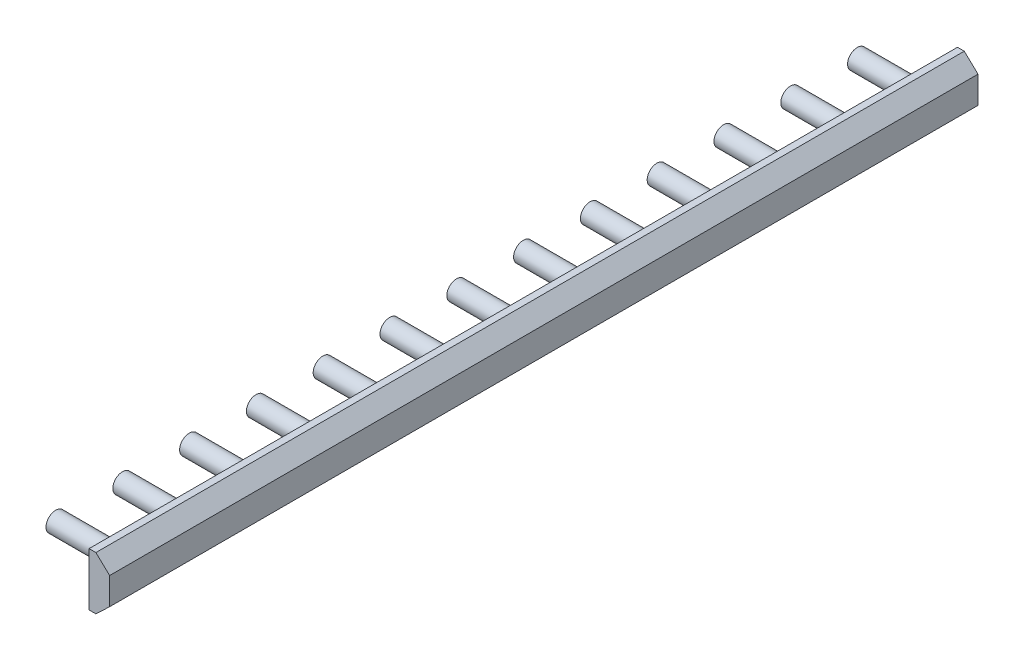
SolidWorks part; units mm, degrees
ref_plane "Front Plane" through (0, 0, 0) normal (0, 0, 1) x (1, 0, 0)
ref_plane "Top Plane" through (0, 0, 0) normal (0, 1, 0) x (1, 0, 0)
ref_plane "Right Plane" through (0, 0, 0) normal (1, 0, 0) x (0, 0, -1)
sketch "Sketch1" plane through (0, 0, 0) normal (0, 0, 1) x (1, 0, 0)
  line B0 (0, 7.95) -> (2.04, 7.95)
  line B1 (6.1524, 4.048) -> (6.1524, -4.048)
  line B2 (2.04, -7.95) -> (0, -7.95)
  line B3 (0, -7.95) -> (0, 7.95)
  line B4 (2.04, 7.95) -> (6.1524, 4.048)
  line B5 (6.1524, -4.048) -> (2.04, -7.95)
sketch_block_instance "Extrusion Profile-1"
sketch_block "Extrusion Profile" parameters "D1"=8.44, "D2"=2.6, "D3"=6, "D4"=16.7, "D6"=5.6686, "D7"=2.0404, "D8"=8.0963, "D9"=15.9, "D5"=2.4157
extrude "Boss-Extrude1" add sketch "Sketch1" along normal blind 260
sketch "Sketch2" plane through (0, 0, 0) normal (-1, 0, 0) x (0, 0, 1)
  circle A0 centre (10, 0) radius 2.9
  circle A1 centre (30, 0) radius 2.9
  circle A2 centre (50, 0) radius 2.9
  circle A3 centre (70, 0) radius 2.9
  circle A4 centre (90, 0) radius 2.9
  circle A5 centre (110, 0) radius 2.9
  circle A6 centre (130, 0) radius 2.9
  circle A7 centre (150, 0) radius 2.9
  circle A8 centre (170, 0) radius 2.9
  circle A9 centre (190, 0) radius 2.9
  circle A10 centre (210, 0) radius 2.9
  circle A11 centre (230, 0) radius 2.9
  circle A12 centre (250, 0) radius 2.9
  dimension "D2" = 5.8
  dimension "D1" = 10
  dimension "D4" = 20
  dimension "D3" = 13
extrude "Boss-Extrude2" add sketch "Sketch2" along normal blind 20
sketch "Sketch3" [suppressed] plane through (0, 0, 0) normal (-1, 0, 0) x (0, 0, 1)
  line L0 (190, 0) -> (210, 0) construction
  line L1 (200, 0) -> (200, 7.95) construction
  line L2 (260, 7.95) -> (0, 7.95) construction
  line L3 (200, 7.95) -> (200, 7)
  line L4 (200, 7) -> (100, 7)
  line L5 (100, 7) -> (100, 7.95)
  line L6 (100, 7.95) -> (200, 7.95)
  line L7 (90, 0) -> (110, 0) construction
  line L8 (100, 0) -> (100, 7) construction
  dimension "D1" = 7
extrude "Cut-Extrude1" [suppressed] cut sketch "Sketch3" against normal through all
chamfer "Chamfer1" [suppressed] distance 3 angle 45
fillet "Fillet1" [suppressed] radius 8
sketch "Sketch4" [suppressed] plane through (0, 0, 0) normal (-1, 0, 0) x (0, 0, 1)
  line L0 (250, 0) -> (230, 0) construction
  line L1 (250, 0) -> (270, 0) construction
  circle A0 centre (270, 0) radius 2.9
  circle A1 centre (250, 0) radius 2.9 construction
  circle A2 centre (290, 0) radius 2.9
  circle A3 centre (310, 0) radius 2.9
  circle A4 centre (330, 0) radius 2.9
  dimension "D2" = 20
  dimension "D1" = 4
extrude "Boss-Extrude3" [suppressed] add sketch "Sketch4" along normal blind 20
